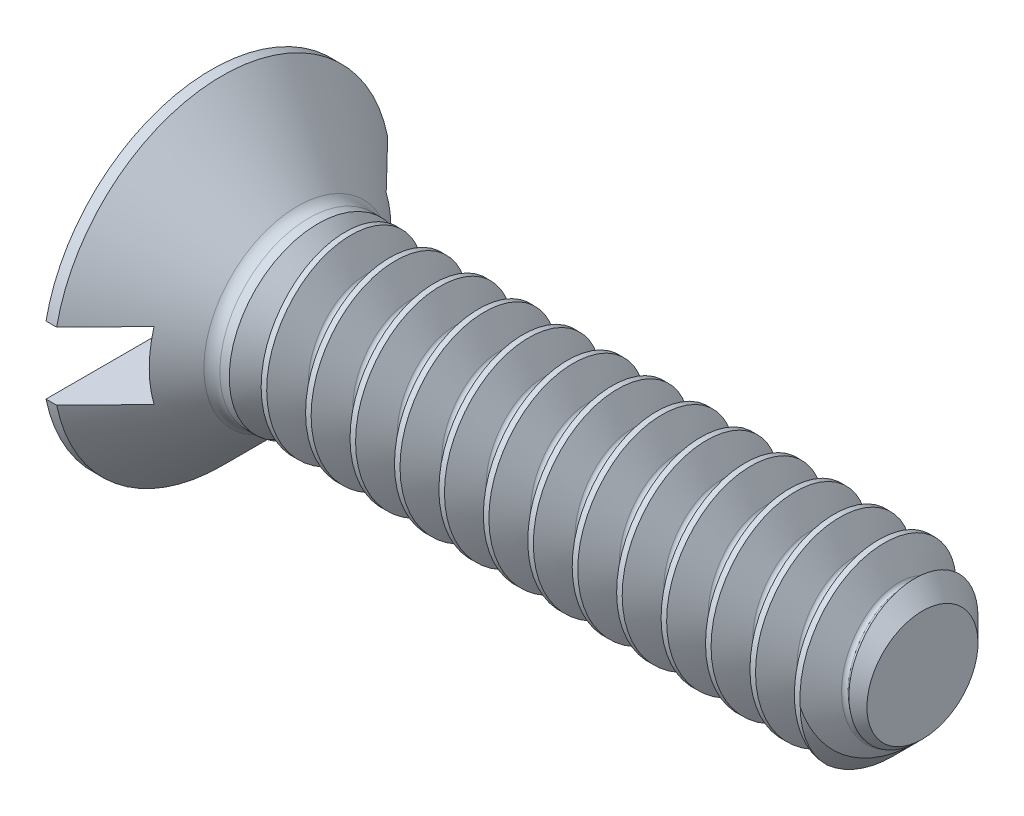
SolidWorks part; units mm, degrees
ref_plane "Front Plane" through (0, 0, 0) normal (0, 0, 1) x (1, 0, 0)
ref_plane "Top Plane" through (0, 0, 0) normal (0, 1, 0) x (1, 0, 0)
ref_plane "Right Plane" through (0, 0, 0) normal (1, 0, 0) x (0, 0, -1)
sketch "Sketch1" plane through (0, 0, 0) normal (0, 0, 1) x (1, 0, 0)
  line L0 (-2, 0) -> (2, 0) construction
  line L1 (-2, 0) -> (-1.4, 0) construction
  line L2 (-2, -0.95) -> (-2, 0.95) construction
  line L3 (2, 0.5) -> (2, -0.5) construction
  line L4 (2, 0.5) -> (1.75, 0.5) construction
  line L5 (-2, 0.95) -> (-1.4, 0.35) construction
  line L6 (-2, -0.95) -> (-1.4, -0.35) construction
  line L7 (-1.4, 0.5) -> (-1.4, -0.5) construction
  point P0 (1.625, -0.5)
  point P4 (0, 0)
  point P9 (-2, 0)
  point P12 (2, 0)
  point P17 (-2, -0.19)
  point P18 (-1.67, 0)
  dimension "Head Height" = 0.6
  dimension "Head Diameter" = 1.9
  dimension "Thread Diameter" = 1
  dimension "Thread Pitch" = 0.25
  dimension "D1" = 0.375
  dimension "Countersink Angle" = 90
  dimension "Length" = 4
  dimension "Slot Width" = 0.38
  dimension "Slot Depth" = 0.33
sketch "Sketch2" plane through (0, 0, 0) normal (0, 0, 1) x (1, 0, 0)
  line L2 (-2, 0) -> (2, 0)
  line L3 (2, 0) -> (2, 0.5)
  line L4 (2, 0.5) -> (-1.4, 0.5)
  line L6 (-2, 0) -> (-2, 0.95)
  line L9 (-2, 0.95) -> (-1.94, 0.95)
  line L10 (-1.94, 0.95) -> (-1.49, 0.5)
  line L11 (-1.49, 0.5) -> (-1.4, 0.5)
  line L12 (-2, 0.95) -> (-1.4, 0.35) construction
  dimension "D1" = 0.06
  dimension "D2" = 0.09
revolve "Revolve1" add sketch "Sketch2" angle 360 about L2
sketch "Sketch3" plane through (0, 0, 0) normal (0, 0, 1) x (1, 0, 0)
  line L0 (-2, -0.19) -> (-2, 0.19)
  line L1 (-2, -0.95) -> (-2, 0.95) construction
  line L2 (-2, 0.19) -> (-1.67, 0.19)
  line L3 (-1.67, 0.19) -> (-1.67, -0.19)
  line L4 (-1.67, -0.19) -> (-2, -0.19)
  point P6 (-2, 0)
  dimension "D1" = 0.33
  dimension "D2" = 0.38
extrude "Cut-Extrude1" cut sketch "Sketch3" against normal through all both and the other way through all
sketch "Sketch6" plane through (-1.67, 0, 0) normal (-1, 0, 0) x (0, 0, 1)
  line L0 (-0.95, 0) -> (0.95, 0) construction
  point P4 (0, 0)
  dimension "D1" = 1.9
sketch "Sketch7" plane through (0, 0, 0) normal (0, 0, 1) x (1, 0, 0)
  line L0 (-2, 0) -> (2, 0) construction
  line L1 (-1.94, 0.95) -> (-1.49, 0.5) construction
  line L2 (-2, 0) -> (2, 0) construction
  line L3 (-1.94, 0.95) -> (-1.49, 0.5)
  line L4 (-1.94, -0.95) -> (-1.49, -0.5)
  line L5 (-1.94, -0.95) -> (-2, -1.01)
  line L6 (-2, -1.01) -> (-2, 1.01) construction
  line L7 (-2, 1.01) -> (-1.94, 0.95)
  point P4 (-1.4, 0.5)
  point P5 (-1.4, -0.5)
fillet "Fillet1" radius 0.09 1 edges at (-1.49, -0.5, 0)
ref_plane "Plane1" through (-1.4, 0, 0) normal (1, 0, 0) x (0, 0, -1)
split "Split1" trim tools "Plane1" bodies to split 105 resulting bodies 106 107
sketch "Sketch4" plane through (2, 0, 0) normal (1, 0, 0) x (0, 0, -1)
  circle A0 centre (0, 0) radius 0.5 construction
  circle A1 centre (0, 0) radius 0.5
  point P3 (0, 0.5)
curve "Helix/Spiral1" pitch 0.25 height 4 radius 0.5 centre (2, 0, 0) axis (-1, 0, 0) start towards (0, 1, 0)
chamfer "Chamfer1" distance 0.1875 angle 45 1 edges at (2, -0.5, 0)
sketch "Sketch8" plane through (0, 0, 0) normal (0, 0, 1) x (1, 0, 0)
  line L0 (1.9844, 0.5271) -> (2.1094, 0.3106) construction
  line L1 (2.1094, 0.3106) -> (2.2344, 0.5271) construction
  line L2 (2.2344, 0.5271) -> (1.9844, 0.5271) construction
  line L3 (2.1094, 0.5271) -> (2.1094, 0.5) construction
  line L4 (2.1094, 0.5) -> (2.1094, 0.3376) construction
  line L5 (2.1094, 0.3376) -> (2.1094, 0.3106) construction
  line L6 (2.1094, 0.5135) -> (2.2266, 0.5135) construction
  line L7 (2.1094, 0.5135) -> (1.9922, 0.5135) construction
  line L8 (2, 0.5) -> (2.2188, 0.5) construction
  line L9 (2.0937, 0.3376) -> (2.125, 0.3376) construction
  line L14 (2.1328, 0.3512) -> (2.2344, 0.5271)
  line L15 (2.0859, 0.3512) -> (1.9922, 0.5135)
  line L16 (1.9922, 0.5135) -> (2.2344, 0.5271)
  arc A0 (2.0859, 0.3512) -> (2.1094, 0.3376) centre (2.1094, 0.3647) ccw
  arc A1 (2.1328, 0.3512) -> (2.1094, 0.3376) centre (2.1094, 0.3647) cw
  dimension "D1" = 0.25
  dimension "D2" = 0.0312
sweep "Cut-Sweep1" cut profiles "Sketch8" path "Helix/Spiral1" align with end faces yes
sketch "Sketch9" plane through (-1.4, 0, 0) normal (1, 0, 0) x (0, 0, -1)
  circle A1 centre (0, 0) radius 0.5
  circle A2 centre (0, 0) radius 0.5
  dimension "D1" = 0
extrude "Boss-Extrude1" add sketch "Sketch9" along normal through all draft 45
equation "\"D1@Sketch3\"=\"Slot Depth@Sketch1\""
equation "\"D3@Helix/Spiral1\"=\"Length@Sketch1\""
equation "\"D4@Helix/Spiral1\" = \"Thread Pitch@Sketch1\""
equation "\"D1@Chamfer1\" = \"Thread Pitch@Sketch1\" * 0.75"
equation "\"D1@Fillet1\"=\"D2@Sketch2\""
equation "\"D1@Sketch6\" = \"Head Diameter@Sketch1\""
equation "\"D1@Sketch1\"=\"Thread Pitch@Sketch1\" * 1.5"
equation "\"D1@Sketch2\"=\"Head Height@Sketch1\"*0.1"
equation "\"Thread Count\"= \"Length@Sketch1\" * 0.4 / \"Thread Pitch@Sketch1\""
equation "\"Rounded Thread Count\"= IIF ( \"Thread Count\" - int ( \"Thread Count\" ) > 0 , int ( \"Thread Count\" ) + 1 , \"Thread Count\" )"
equation "\"Segment Length\"= \"Thread Pitch@Sketch1\" * \"Rounded Thread Count\""
equation "\"D2@Sketch3\"=\"Slot Width@Sketch1\""
equation "\"D2@Sketch8\"=\"D1@Sketch8\"/8"
equation "\"D1@Sketch8\"=\"Thread Pitch@Sketch1\""
equation "\"Slot Width@Sketch1\"=\"Head Diameter@Sketch1\"*.2"
equation "\"Slot Depth@Sketch1\"=\"Head Height@Sketch1\"*.55"
